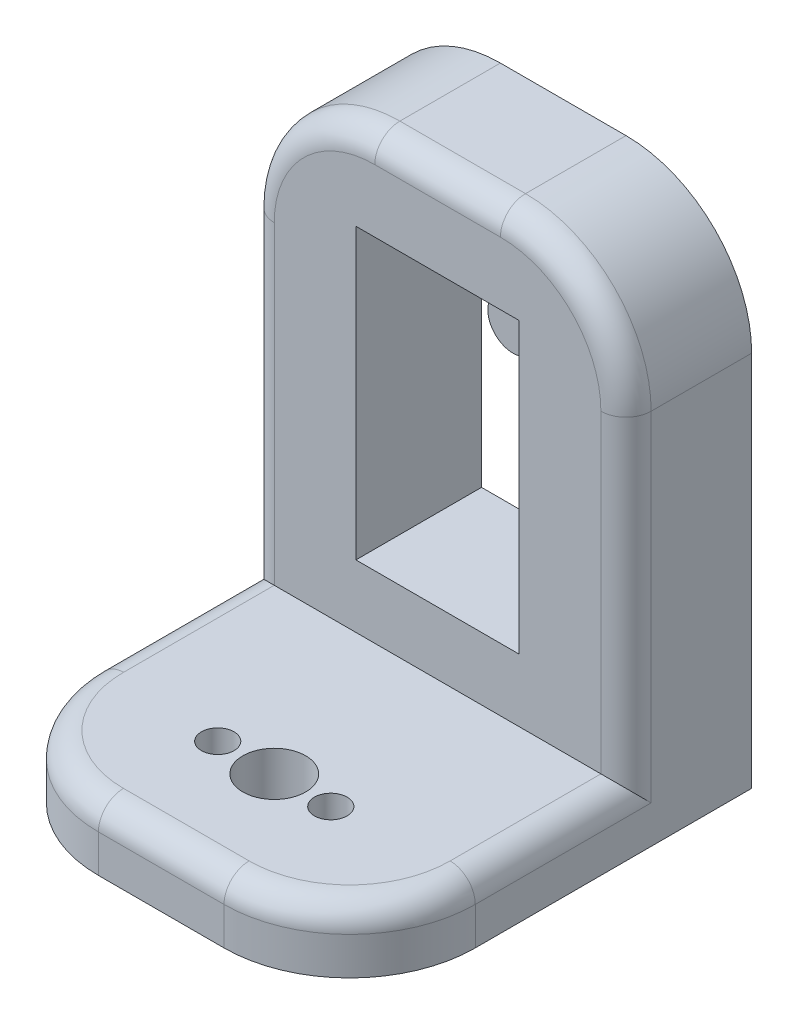
SolidWorks part; units mm, degrees
other "Markup1"
sketch "Sketch6" plane through (35, 0, -3.5) normal (0.0521, -0.007, 0.9986) x (0.9986, 0, -0.0521)
ref_plane "Front Plane" through (0, 0, 0) normal (0, 0, 1) x (1, 0, 0)
ref_plane "Top Plane" through (0, 0, 0) normal (0, 1, 0) x (1, 0, 0)
ref_plane "Right Plane" through (0, 0, 0) normal (1, 0, 0) x (0, 0, -1)
sketch "Sketch1" plane through (0, 0, 0) normal (0, 1, 0) x (1, 0, 0)
  line L0 (0, 15) -> (30, 15) construction
  line L1 (0, 0) -> (30, 0)
  line L2 (0, 0) -> (0, 30)
  line L3 (0, 30) -> (30, 30)
  line L4 (30, 0) -> (30, 30)
  line L5 (15, 30) -> (15, 0) construction
  circle A0 centre (15, 15) radius 2.5
  circle A1 centre (10.5, 15) radius 1.3
  circle A2 centre (19.5, 15) radius 1.3
  dimension "D3" = 2.6
  dimension "D4" = 5
  dimension "D1" = 30
  dimension "D2" = 30
  dimension "D5" = 9
extrude "Boss-Extrude1" add sketch "Sketch1" along normal blind 5 contours L1 L4 L3 L2 A2 A1 A0 region at (0.4243, 0, -15)
sketch "Sketch2" plane through (30, 0, 0) normal (1, 0, 0) x (0, 0, -1)
  line L1 (28, 0) -> (38, 0)
  line L2 (28, 0) -> (28, 40)
  line L3 (28, 40) -> (38, 40)
  line L4 (38, 0) -> (38, 40)
  line L5 (0, 0) -> (30, 0) construction
  line L6 (30, 5) -> (30, 0) construction
  dimension "D1" = 10
  dimension "D2" = 40
  dimension "D3" = 2
extrude "Boss-Extrude2" add sketch "Sketch2" against normal up to surface (30 mm away) up to face at (0, 2.5, -15)
sketch "Sketch3" plane through (0, 0, -38) normal (0, 0, -1) x (-1, 0, 0)
  line L0 (0, 0) -> (-30, 0) construction
  line L1 (-21.5, 33) -> (-8.5, 33)
  line L2 (-21.5, 33) -> (-21.5, 10)
  line L3 (-21.5, 10) -> (-8.5, 10)
  line L4 (-8.5, 33) -> (-8.5, 10)
  circle A0 centre (-15, 26.5) radius 6.5
  circle A1 centre (-15, 35.5) radius 1.05
  circle A2 centre (-15, 7.5) radius 1.05
  circle A3 centre (-15, 26.5) radius 2
  point P10 (-15, 0)
  dimension "D1" = 13
  dimension "D4" = 2.1
  dimension "D7" = 4
  dimension "D2" = 23
  dimension "D3" = 10
  dimension "D5" = 9
  dimension "D6" = 19
extrude "Cut-Extrude1" cut sketch "Sketch3" against normal through all contours L4 L3 L2 L1
extrude "Cut-Extrude2" cut sketch "Sketch3<3>" against normal blind 8 contours A1 | A2
sketch "Sketch3<3>" plane through (0, 0, -38) normal (0, 0, -1) x (-1, 0, 0) same geometry as "Sketch3"
extrude "Boss-Extrude3" add sketch "Sketch3<6>" against normal blind 4 separate body contours A3 region at (15, 26.5, -38)
sketch "Sketch3<6>" plane through (0, 0, -38) normal (0, 0, -1) x (-1, 0, 0) same geometry as "Sketch3"
sketch "Sketch5" plane through (0, 5, 0) normal (0, 1, 0) x (1, 0, 0)
  line L0 (0, 0) -> (0, 28) construction
  line L1 (0, 6) -> (30, 6)
  line L2 (0, 6) -> (0, 0)
  line L3 (0, 0) -> (30, 0)
  line L4 (30, 6) -> (30, 0)
  line L5 (15, 15) -> (0, 15) construction
  dimension "D1" = 9
extrude "Cut-Extrude4" cut sketch "Sketch5" against normal up to next (5 mm away)
fillet "Fillet4" radius 10 4 edges at (0, 40, -33) (30, 40, -33) (0, 2.5, -6) (30, 2.5, -6)
fillet "Fillet5" radius 2 10 edges at (30, 5, -22) (27.0711, 5, -8.9289) (0, 5, -22) (2.9289, 5, -8.9289) (0, 17.5, -28) (2.9289, 37.0711, -28) (15, 40, -28) (27.0711, 37.0711, -28) (15, 5, -6) (30, 17.5, -28)
